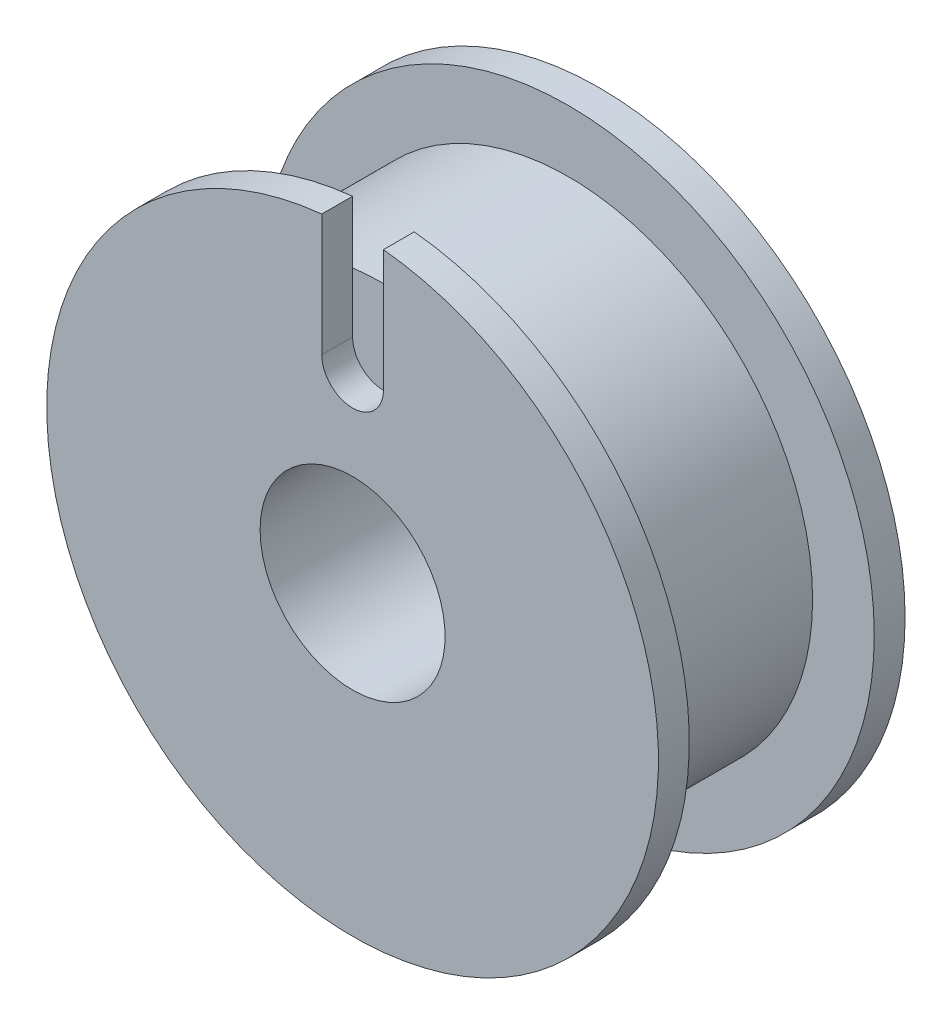
SolidWorks part; units mm, degrees
ref_plane "Front Plane" through (0, 0, 0) normal (0, 0, 1) x (1, 0, 0)
ref_plane "Top Plane" through (0, 0, 0) normal (0, 1, 0) x (1, 0, 0)
ref_plane "Right Plane" through (0, 0, 0) normal (1, 0, 0) x (0, 0, -1)
sketch "Sketch1" plane through (0.9276, 0, 0) normal (1, 0, 0) x (0, 0, -1)
  line L0 (104.775, 29.0452) -> (-10.6045, 29.0452) construction
  line L1 (69.967, 44.7932) -> (69.967, 13.2972) construction
  line L2 (71.5545, 44.7932) -> (69.967, 44.7932) construction
  line L3 (71.5545, 44.7932) -> (71.5545, 13.2972) construction
  line L4 (71.5545, 41.6182) -> (81.0795, 41.6182) construction
  line L5 (81.0795, 44.7932) -> (81.0795, 13.2972) construction
  line L6 (81.0795, 44.7932) -> (82.667, 44.7932) construction
  line L7 (82.667, 44.7932) -> (82.667, 13.2972) construction
  line L8 (22.225, 29.0452) -> (9.525, 29.0452)
  line L9 (69.967, 44.7932) -> (69.967, 33.8077)
  line L10 (71.5545, 44.7932) -> (69.967, 44.7932)
  line L11 (71.5545, 44.7932) -> (71.5545, 41.6182)
  line L12 (71.5545, 41.6182) -> (81.0795, 41.6182)
  line L13 (81.0795, 44.7932) -> (81.0795, 41.6182)
  line L14 (81.0795, 44.7932) -> (82.667, 44.7932)
  line L15 (82.667, 44.7932) -> (82.667, 33.8077)
  line L16 (104.775, 33.8077) -> (-1.5875, 33.8077) construction
  line L17 (104.775, 33.8077) -> (-1.5875, 33.8077)
revolve "Revolve1" add sketch "Sketch1" angle 360 about L8 region at (0.9276, 38.2197, -76.317)
sketch "Sketch2" plane through (0, 0, -69.967) normal (0, 0, -1) x (-1, 0, 0)
  line L0 (-0.9276, 44.7932) -> (-0.9276, 13.2972) construction
  line L1 (-0.9276, 44.7932) -> (-0.9276, 13.2972)
  line L2 (-0.9276, 44.7932) -> (-0.9276, 38.4432) construction
  line L3 (0.6599, 44.7932) -> (0.6599, 38.4432)
  line L4 (-2.5151, 44.7932) -> (-2.5151, 38.4432)
  arc A0 (0.6599, 44.7932) -> (-2.5151, 44.7932) centre (-0.9276, 44.7932) ccw
  arc A1 (-2.5151, 38.4432) -> (0.6599, 38.4432) centre (-0.9276, 38.4432) ccw
  point P2 (-0.9276, 41.6182)
  circle M11 centre (-0.9276, 29.0452) radius 15.748
  dimension "D1" = 1.5875
  dimension "D2" = 6.35
extrude "Cut-Extrude1" cut sketch "Sketch2" along normal up to surface (1.5875 mm away) contours A1 L1 L3 M11 | A1 L4 L1 M11 region at (0.155, 40.9732, -69.967) region at (1.7002, 40.9732, -69.967) up to face at (-11.6454, 29.0452, -71.5545)
